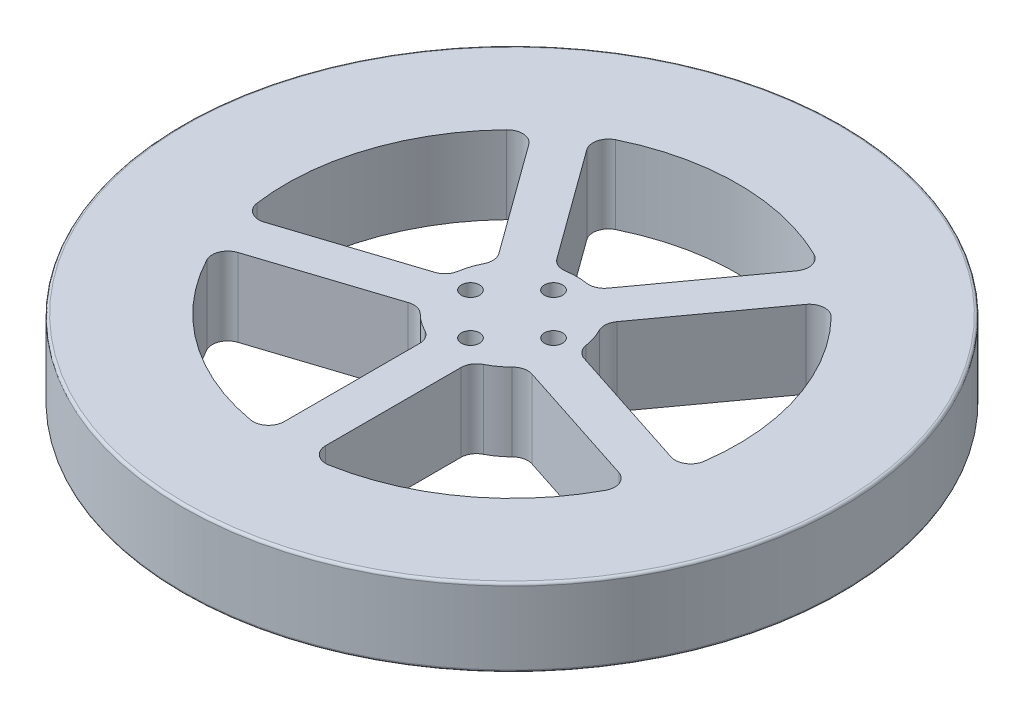
SolidWorks part; units mm, degrees
material "Polyethylene Cross-Linked"
ref_plane "Front Plane" through (0, 0, 0) normal (0, 0, 1) x (1, 0, 0)
ref_plane "Top Plane" through (0, 0, 0) normal (0, 1, 0) x (1, 0, 0)
ref_plane "Right Plane" through (0, 0, 0) normal (1, 0, 0) x (0, 0, -1)
sketch "Sketch2" plane through (0, 0, 0) normal (0, 1, 0) x (1, 0, 0)
  circle A0 centre (0, 0) radius 63.5
  point P13 (0, 0)
  point P19 (0, 0)
  dimension "D1" = 127
extrude "Boss-Extrude1" add sketch "Sketch2" along normal blind 15 contours A0 region at (0, 0, 0)
sketch "Sketch3" plane through (0, 15, 0) normal (0, 1, 0) x (1, 0, 0)
  circle A0 centre (0, 0) radius 8 construction
  circle A1 centre (0, 8) radius 1.75
  circle A2 centre (8, 0) radius 1.75
  circle A3 centre (0, -8) radius 1.75
  circle A4 centre (-8, 0) radius 1.75
  point P14 (0, 0)
  dimension "D1" = 16
  dimension "D2" = 3.5
  dimension "D3" = 4
extrude "Cut-Extrude1" cut sketch "Sketch3" against normal through all
fillet "Fillet2" radius 0.5 2 edges at (0, 15, 63.5) (0, 0, 63.5)
sketch "Sketch5" plane through (0, 0, 0) normal (0, -1, 0) x (1, 0, 0)
  line L0 (0, 0) -> (0, 43.5)
  line L1 (-4, 11.8427) -> (-4, 43.3157)
  line L2 (4, 11.8427) -> (4, 43.3157)
  line L3 (-4, 27.5792) -> (4, 27.5792) construction
  line L4 (0, 0) -> (41.371, 13.4422)
  line L5 (10.027, 7.4638) -> (39.9596, 17.1895)
  line L6 (12.4992, -0.1446) -> (42.4317, 9.5811)
  line L7 (24.9933, 12.3267) -> (27.4655, 4.7182) construction
  line L8 (0, 0) -> (25.5687, -35.1922)
  line L9 (10.197, -7.2298) -> (28.6964, -32.692)
  line L10 (3.7249, -11.9321) -> (22.2243, -37.3943)
  line L11 (19.4467, -19.9609) -> (12.9746, -24.6632) construction
  line L12 (0, 0) -> (-25.5687, -35.1922)
  line L13 (-3.7249, -11.9321) -> (-22.2243, -37.3943)
  line L14 (-10.197, -7.2298) -> (-28.6964, -32.692)
  line L15 (-12.9746, -24.6632) -> (-19.4467, -19.9609) construction
  line L16 (0, 0) -> (-41.371, 13.4422)
  line L17 (-12.4992, -0.1446) -> (-42.4317, 9.5811)
  line L18 (-10.027, 7.4638) -> (-39.9596, 17.1895)
  line L19 (-27.4655, 4.7182) -> (-24.9933, 12.3267) construction
  arc A0 (-42.4317, 9.5811) -> (-28.6964, -32.692) centre (0, 0) ccw
  arc A1 (-12.4992, -0.1446) -> (-10.197, -7.2298) centre (0, 0) ccw
  circle A2 centre (0, 0) radius 63.5 construction
  arc A3 (-22.2243, -37.3943) -> (22.2243, -37.3943) centre (0, 0) ccw
  arc A4 (28.6964, -32.692) -> (42.4317, 9.5811) centre (0, 0) ccw
  arc A5 (39.9596, 17.1895) -> (4, 43.3157) centre (0, 0) ccw
  arc A6 (-4, 43.3157) -> (-39.9596, 17.1895) centre (0, 0) ccw
  arc A7 (-4, 11.8427) -> (-10.027, 7.4638) centre (0, 0) ccw
  arc A8 (10.027, 7.4638) -> (4, 11.8427) centre (0, 0) ccw
  arc A9 (10.197, -7.2298) -> (12.4992, -0.1446) centre (0, 0) ccw
  arc A10 (-3.7249, -11.9321) -> (3.7249, -11.9321) centre (0, 0) ccw
  point P43 (0, 0)
  dimension "D1" = 25
  dimension "D2" = 20
  dimension "D3" = 8
  dimension "D4" = 5
extrude "Cut-Extrude3" cut sketch "Sketch5" against normal up to next contours A7 L1 A6 L18 | A8 L5 A5 L2 | A9 L9 A4 L6 | A10 L13 A3 L10 | A1 L17 A0 L14 region at (-17.8657, 0, 24.5901) region at (17.8657, 0, 24.5901) region at (28.9074, 0, -9.3926) region at (0, 0, -30.395) region at (-28.9074, 0, -9.3926)
fillet "Fillet3" radius 3 20 edges at (42.4317, 7.5, 9.5811) (12.4992, 7.5, -0.1446) (10.197, 7.5, -7.2298) (28.6964, 7.5, -32.692) (-42.4317, 7.5, 9.5811) (-39.9596, 7.5, 17.1895) (-4, 7.5, 43.3157) (4, 7.5, 43.3157) (-10.027, 7.5, 7.4638) (4, 7.5, 11.8427) (10.027, 7.5, 7.4638) (-28.6964, 7.5, -32.692) (3.7249, 7.5, -11.9321) (-3.7249, 7.5, -11.9321) (-22.2243, 7.5, -37.3943) (-10.197, 7.5, -7.2298) (-12.4992, 7.5, -0.1446) (-4, 7.5, 11.8427) (39.9596, 7.5, 17.1895) (22.2243, 7.5, -37.3943)
